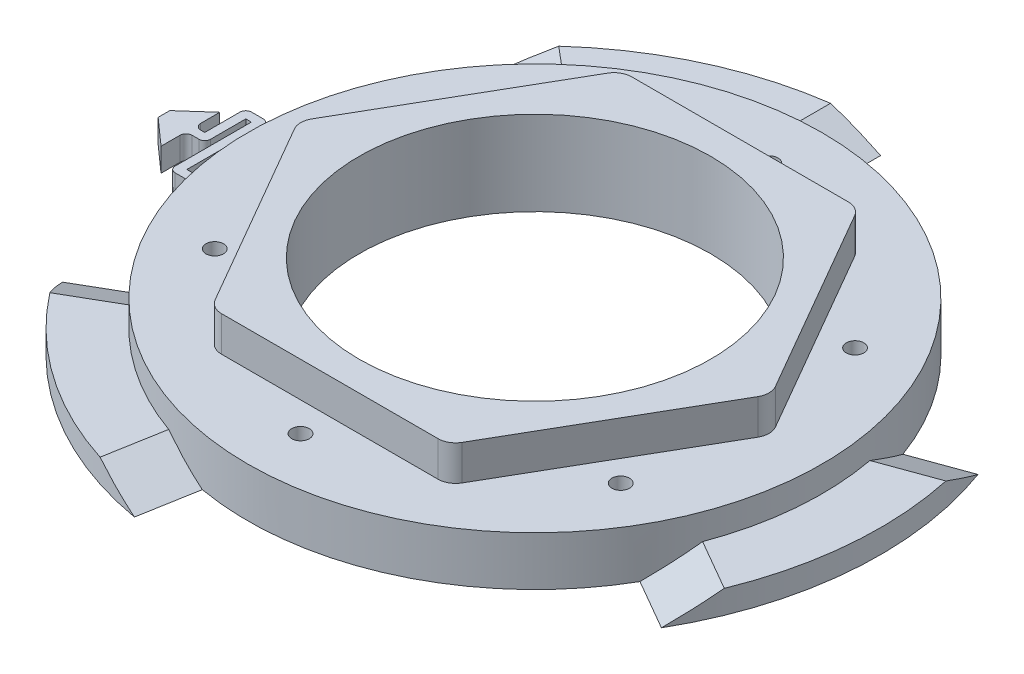
SolidWorks part; units mm, degrees
ref_plane "Ebene vorne" through (0, 0, 0) normal (0, 0, 1) x (1, 0, 0)
ref_plane "Ebene oben" through (0, 0, 0) normal (0, 1, 0) x (1, 0, 0)
ref_plane "Ebene rechts" through (0, 0, 0) normal (1, 0, 0) x (0, 0, -1)
sketch "Skizze1" plane through (0, 0, 0) normal (0, 1, 0) x (1, 0, 0)
  line L0 (0, 0) -> (0, 49) construction
  line L1 (0, 0) -> (-37.5362, 31.4966) construction
  line L2 (-37.5362, 31.4966) -> (-45.1966, 37.9245)
  line L3 (0, 49) -> (0, 59)
  line L4 (46.0449, 16.759) -> (55.4419, 20.1792)
  line L5 (42.4352, -24.5) -> (51.0955, -29.5)
  line L6 (-8.5088, -48.2556) -> (-10.2452, -58.1037)
  line L7 (-42.4352, -24.5) -> (-51.0955, -29.5)
  arc A0 (-51.0955, -29.5) -> (-10.2452, -58.1037) centre (0, 0) ccw
  arc A1 (-8.5088, -48.2556) -> (42.4352, -24.5) centre (0, 0) ccw
  arc A2 (0, 59) -> (-45.1966, 37.9245) centre (0, 0) ccw
  arc A3 (51.0955, -29.5) -> (55.4419, 20.1792) centre (0, 0) ccw
  arc A4 (46.0449, 16.759) -> (0, 49) centre (0, 0) ccw
  arc A5 (-37.5362, 31.4966) -> (-42.4352, -24.5) centre (0, 0) ccw
  point P18 (0, 0)
  dimension "D1" = 118
  dimension "D2" = 98
  dimension "D3" = 50
  dimension "D4" = 3
extrude "Aufsatz-Linear austragen1" add sketch "Skizze1" along normal blind 4
sketch "Skizze2" plane through (0, 4, 0) normal (0, 1, 0) x (1, 0, 0)
  circle A0 centre (0, 0) radius 49
extrude "Aufsatz-Linear austragen2" add sketch "Skizze2" along normal blind 4.4
chamfer "Fase1" distance 4 distance2 8 6 edges at (46.7654, 4, 27) (50.7434, 4, -18.4691) (0, 4, -54) (-41.3664, 4, -34.7105) (-9.377, 4, 53.1796) (-46.7654, 4, 27) first distance on face at (46.7654, 2, 27) first distance on face at (50.7434, 2, -18.4691) first distance on face at (0, 2, -54) first distance on face at (-41.3664, 2, -34.7105) first distance on face at (-9.377, 2, 53.1796) first distance on face at (-46.7654, 2, 27)
sketch "Skizze3" plane through (0, 8.4, 0) normal (0, 1, 0) x (1, 0, 0)
  line L0 (0, 0) -> (40.4145, 0) construction
  line L1 (40.4145, 0) -> (20.2073, 35)
  line L2 (20.2073, 35) -> (-20.2073, 35)
  line L3 (-20.2073, 35) -> (-40.4145, 0)
  line L4 (-40.4145, 0) -> (-20.2073, -35)
  line L5 (-20.2073, -35) -> (20.2073, -35)
  line L6 (20.2073, -35) -> (40.4145, 0)
  circle A0 centre (0, 0) radius 35 construction
  dimension "D1" = 70
extrude "Aufsatz-Linear austragen3" add sketch "Skizze3" along normal blind 6
sketch "Skizze4" plane through (0, 14.4, 0) normal (0, 1, 0) x (1, 0, 0)
  circle A0 centre (0, 0) radius 30
  dimension "D1" = 60
extrude "Schnitt-Linear austragen2" cut sketch "Skizze4" against normal through all
sketch "Skizze5" plane through (0, 0, 0) normal (0, -1, 0) x (1, 0, 0)
  line L0 (-49, 0) -> (-51.4475, 0) construction
  line L1 (-51.4475, 0) -> (-51.4475, 7) construction
  line L2 (-51.4475, 7) -> (-53.895, 7) construction
  line L3 (-53.895, 7) -> (-53.895, -7) construction
  line L4 (-53.895, -7) -> (-56.3425, -7) construction
  line L5 (-56.3425, -7) -> (-56.3425, 0) construction
  line L6 (-56.3425, 0) -> (-61.0453, 0) construction
  line L7 (-51.4475, 0) -> (-56.3425, 0) construction
  line L8 (-58.7878, -5) -> (-63.3028, -5)
  line L9 (-58.7878, -5) -> (-58.7878, -0.75)
  line L10 (-58.7878, 5) -> (-63.3028, 5)
  line L11 (-63.3028, -5) -> (-63.3028, 5)
  line L12 (-58.7878, -5) -> (-63.3028, 5) construction
  line L13 (-58.7878, 5) -> (-63.3028, -5) construction
  line L14 (-48.9943, 0.75) -> (-50.6975, 0.75)
  line L15 (-50.6975, 0.75) -> (-50.6975, 7.75)
  line L16 (-50.6975, 7.75) -> (-54.645, 7.75)
  line L17 (-54.645, 7.75) -> (-54.645, -6.25)
  line L18 (-54.645, -6.25) -> (-55.5925, -6.25)
  line L19 (-55.5925, -6.25) -> (-55.5925, 0.75)
  line L20 (-55.5925, 0.75) -> (-58.7878, 0.75)
  line L21 (-48.9943, -0.75) -> (-52.1975, -0.75)
  line L22 (-52.1975, -0.75) -> (-52.1975, 6.25)
  line L23 (-52.1975, 6.25) -> (-53.145, 6.25)
  line L24 (-53.145, 6.25) -> (-53.145, -7.75)
  line L25 (-53.145, -7.75) -> (-57.0925, -7.75)
  line L26 (-57.0925, -7.75) -> (-57.0925, -0.75)
  line L27 (-57.0925, -0.75) -> (-58.7878, -0.75)
  line L28 (-58.7878, 0.75) -> (-58.7878, 5)
  line L29 (-49, -0.75) -> (-52.1975, -0.75) construction
  line L30 (-57.0925, -0.75) -> (-61.0453, -0.75) construction
  line L31 (-55.5925, 0.75) -> (-61.0453, 0.75) construction
  line L32 (-49, 0.75) -> (-50.6975, 0.75) construction
  arc A0 (-48.9943, 0.75) -> (-48.9943, -0.75) centre (0, 0) ccw
  circle A1 centre (0, 0) radius 63.5 construction
  circle A2 centre (0, 0) radius 59 construction
  dimension "D1" = 98
  dimension "D2" = 127
  dimension "D3" = 118
  dimension "D4" = 10
  dimension "D5" = 2.4475
  dimension "D6" = 2.4475
  dimension "D7" = 2.4475
  dimension "D8" = 7
  dimension "D9" = 14
  dimension "D10" = 0.75
  dimension "D11" = 0.75
extrude "Aufsatz-Linear austragen4" add sketch "Skizze5" against normal up to surface (4 mm away) up to face at (-30.3355, 4, 43.3236)
fillet "Verrundung2" radius 1 10 edges at (-48.9943, 2, 0.75) (-48.9943, 2, -0.75) (-58.7878, 2, -0.75) (-58.7878, 2, 0.75) (-55.5925, 2, 0.75) (-50.6975, 2, 7.75) (-54.645, 2, 7.75) (-57.0925, 2, -7.75) (-53.145, 2, -7.75) (-52.1975, 2, -0.75)
chamfer "Fase2" distance 4 distance2 4.5 1 edges at (-63.3028, 2, 5) first distance on face at (-63.3028, 2, 0)
chamfer "Fase3" distance 4.5 distance2 4 1 edges at (-63.3028, 2, -5) first distance on face at (-61.0453, 2, -5)
fillet "Verrundung3" radius 3 6 edges at (-20.2073, 11.4, 35) (20.2073, 11.4, 35) (40.4145, 11.4, 0) (-40.4145, 11.4, 0) (-20.2073, 11.4, -35) (20.2073, 11.4, -35)
sketch "Skizze6" plane through (0, 8.4, 0) normal (0, 1, 0) x (1, 0, 0)
  line L0 (0, 0) -> (0, 40) construction
  circle A0 centre (0, 40) radius 1.5
  circle A1 centre (34.641, 20) radius 1.5
  circle A2 centre (34.641, -20) radius 1.5
  circle A3 centre (0, -40) radius 1.5
  circle A4 centre (-34.641, -20) radius 1.5
  circle A5 centre (-34.641, 20) radius 1.5
  point P5 (42.0907, 14.2983)
  point P16 (0, 0)
  dimension "D1" = 3
  dimension "D2" = 40
  dimension "D3" = 6
extrude "Schnitt-Linear austragen3" cut sketch "Skizze6" against normal through all
